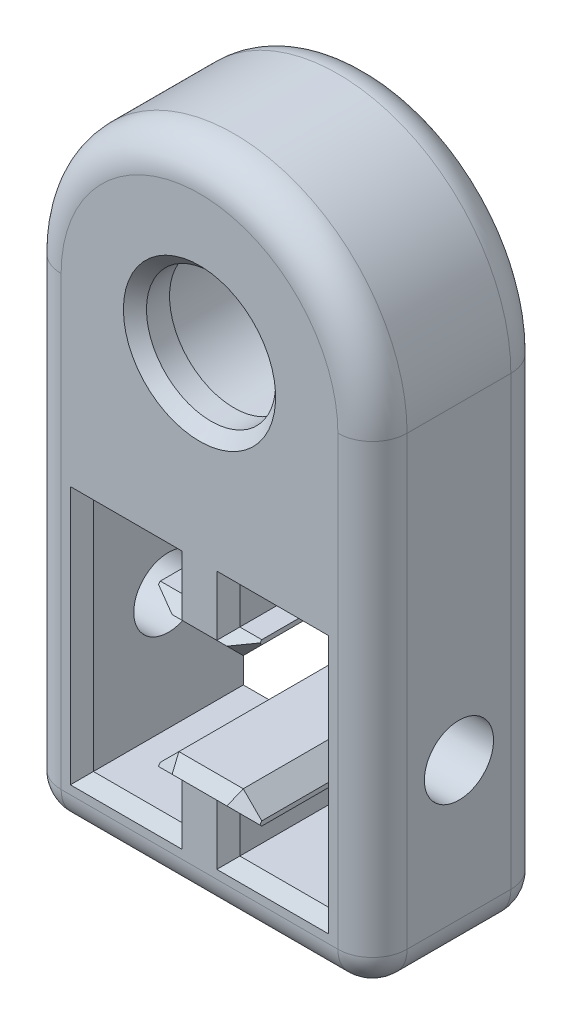
SolidWorks part; units mm, degrees
ref_plane "Front Plane" through (0, 0, 0) normal (0, 0, 1) x (1, 0, 0)
ref_plane "Top Plane" through (0, 0, 0) normal (0, 1, 0) x (1, 0, 0)
ref_plane "Right Plane" through (0, 0, 0) normal (1, 0, 0) x (0, 0, -1)
sketch "Sketch1" plane through (0, 0, 0) normal (0, 0, 1) x (1, 0, 0)
  line L0 (0, -15) -> (0, 15) construction
  line L1 (0, 15) -> (15, 15)
  line L2 (15, 15) -> (15, -14.9496)
  line L3 (15, -14.9496) -> (-15, -14.9496)
  line L4 (-15, -14.9496) -> (-15, 15)
  line L5 (-15, 15) -> (0, 15)
  line L6 (0, -10.2) -> (0, 10.2) construction
  line L7 (0, 10.2) -> (-10.2, 10.2) construction
  line L8 (-10.2, 10.2) -> (-2.5, 10.2)
  line L9 (-2.5, 10.2) -> (-2.5, 7)
  line L10 (-2.5, 7) -> (0, 7) construction
  line L11 (-2.5, 7) -> (-4.4, 7)
  line L12 (-4.4, 7) -> (-4.4, 6.61)
  line L13 (-4.4, 6.61) -> (-2.79, 5)
  line L14 (-2.79, 5) -> (0, 5) construction
  line L15 (-2.79, 5) -> (2.79, 5)
  line L22 (-10.2, 10.2) -> (-10.2, 3)
  line L23 (0, 0) -> (-11.0308, 0) construction
  line L24 (4.4, 6.61) -> (2.79, 5)
  line L25 (4.4, 7) -> (4.4, 6.61)
  line L26 (2.5, 7) -> (4.4, 7)
  line L27 (2.5, 10.2) -> (2.5, 7)
  line L28 (10.2, 10.2) -> (2.5, 10.2)
  line L29 (10.2, 10.2) -> (10.2, 3)
  line L36 (-2.79, -5) -> (0, -5) construction
  line L37 (-2.5, -7) -> (0, -7) construction
  line L38 (0, -10.2) -> (-10.2, -10.2) construction
  line L43 (10.2, -10.2) -> (10.2, -3)
  line L44 (10.2, -10.2) -> (2.5, -10.2)
  line L45 (2.5, -10.2) -> (2.5, -7)
  line L46 (2.5, -7) -> (4.4, -7)
  line L47 (4.4, -7) -> (4.4, -6.61)
  line L48 (4.4, -6.61) -> (2.79, -5)
  line L49 (-10.2, -10.2) -> (-10.2, -3)
  line L54 (-2.79, -5) -> (2.79, -5)
  line L55 (-4.4, -6.61) -> (-2.79, -5)
  line L56 (-4.4, -7) -> (-4.4, -6.61)
  line L57 (-2.5, -7) -> (-4.4, -7)
  line L58 (-2.5, -10.2) -> (-2.5, -7)
  line L59 (-10.2, -10.2) -> (-2.5, -10.2)
  line L60 (-10.2, 3) -> (-10.2, -3)
  line L61 (10.2, -3) -> (10.2, 3)
  point P43 (4, 0)
  point P58 (-4, 0)
  dimension "D1" = 2.5
  dimension "D2" = 2.79
  dimension "D3" = 1.9
  dimension "D4" = 135
  dimension "D5" = 2
  dimension "D6" = 15
  dimension "D7" = 15
  dimension "D8" = 10.2
  dimension "D9" = 90
  dimension "D10" = 3.2
  dimension "D11" = 15
  dimension "D12" = 10.2
extrude "Boss-Extrude1" add sketch "Sketch1" along normal blind 15
sketch "Sketch4" plane through (0, 0, 0) normal (0, 0, -1) x (-1, 0, 0)
  line L0 (0, 15) -> (0, 20) construction
  line L1 (-15, 15) -> (15, 15) construction
  line L2 (0, 20) -> (0, 26.8) construction
  line L3 (-15, 15) -> (-15, 26.8)
  line L4 (15, 26.8) -> (15, 15)
  line L5 (15, 15) -> (-15, 15)
  line L6 (15, -14.9496) -> (-15, -14.9496) construction
  circle A0 centre (0, 26.8) radius 6.8
  arc A1 (-15, 26.8) -> (15, 26.8) centre (0, 26.8) cw
  line M2 (15, 15) -> (-15, 15)
  dimension "D2" = 13.6
  dimension "D3" = 15
  dimension "D1" = 29.9496
  dimension "D4" = 5
extrude "Boss-Extrude2" add sketch "Sketch4" against normal up to surface (15 mm away) contours A1 L3 L4 A0 M2
sketch "Sketch3" plane through (-15, 0, 0) normal (-1, 0, 0) x (0, 0, 1)
  line L0 (7.5, 0) -> (15, 5.9252) construction
  line L1 (0, 26.8) -> (0, -14.9496) construction
  line L2 (0, 0) -> (7.5, 0) construction
  line L3 (15, 26.8) -> (15, -14.9496) construction
  circle A0 centre (7.5, 0) radius 3
  dimension "D1" = 7.5
extrude "Cut-Extrude1" cut sketch "Sketch3" against normal through all
fillet "Fillet1" radius 3 10 edges at (0, -14.9496, 15) (15, 5.9252, 15) (-15, 5.9252, 15) (15, 5.9252, 0) (-15, 5.9252, 0) (0, -14.9496, 0) (15, -14.9496, 7.5) (-15, -14.9496, 7.5) (0, 41.8, 15) (0, 41.8, 0)
sketch "Sketch5" plane through (0, 0, 15) normal (0, 0, 1) x (1, 0, 0)
  line L0 (0, 20) -> (0, 33.6) construction
  circle A0 centre (0, 26.8) radius 6.8 construction
  circle A1 centre (0, 26.8) radius 10
  circle A2 centre (0, 26.8) radius 5.6
extrude "Boss-Extrude3" add sketch "Sketch5" against normal blind 3
chamfer "Chamfer1" distance 1 angle 45 42 edges at (-6.8, 26.8, 0) (-3.595, 5.805, 0) (0, 5, 0) (3.595, 5.805, 0) (3.45, 7, 0) (2.5, 8.6, 0) (6.35, 10.2, 0) (10.2, 0, 0) (6.35, -10.2, 0) (2.5, -8.6, 0) (3.45, -7, 0) (3.595, -5.805, 0) (0, -5, 0) (-3.595, -5.805, 0) (-3.45, -7, 0) (-2.5, -8.6, 0) (-6.35, -10.2, 0) (-10.2, 0, 0) (-6.35, 10.2, 0) (-2.5, 8.6, 0) (-3.45, 7, 0) (-2.5, 8.6, 15) (-6.35, 10.2, 15) (-10.2, 0, 15) (-6.35, -10.2, 15) (-2.5, -8.6, 15) (-3.45, -7, 15) (-3.595, -5.805, 15) (0, -5, 15) (3.595, -5.805, 15) (3.45, -7, 15) (2.5, -8.6, 15) (6.35, -10.2, 15) (10.2, 0, 15) (6.35, 10.2, 15) (2.5, 8.6, 15) (3.45, 7, 15) (3.595, 5.805, 15) (0, 5, 15) (-3.595, 5.805, 15) (-3.45, 7, 15) (5.6, 26.8, 15)
